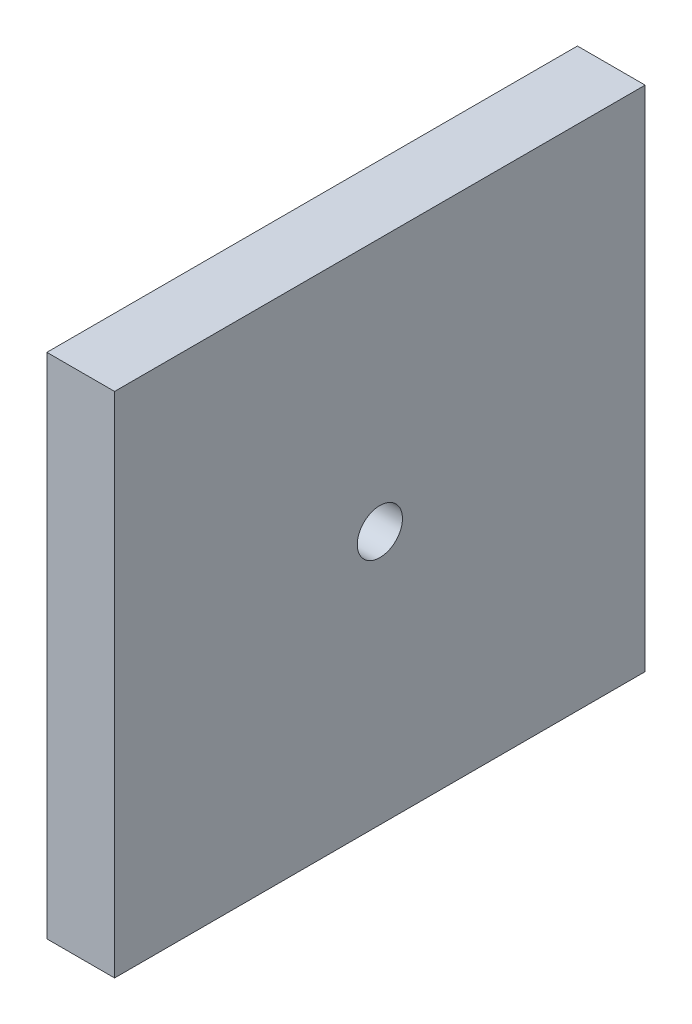
SolidWorks part; units mm, degrees
ref_plane "Ebene vorne" through (0, 0, 0) normal (0, 0, 1) x (1, 0, 0)
ref_plane "Ebene oben" through (0, 0, 0) normal (0, 1, 0) x (1, 0, 0)
ref_plane "Ebene rechts" through (0, 0, 0) normal (1, 0, 0) x (0, 0, -1)
sketch "Sketch1" plane through (0, 0, 0) normal (1, 0, 0) x (0, 0, -1)
  line L0 (0, 39.4227) -> (0, -41.65) construction
  line L1 (-47, 45) -> (47, 45)
  line L2 (-47, 45) -> (-47, -45)
  line L3 (-47, -45) -> (47, -45)
  line L4 (47, 45) -> (47, -45)
  line L5 (48.1091, 0) -> (-28.5091, 0) construction
  dimension "D1" = 94
  dimension "D2" = 90
extrude "Boss-Extrude1" add sketch "Sketch1" along normal blind 12
sketch "Sketch2" plane through (12, 0, 0) normal (1, 0, 0) x (0, 0, -1)
  circle A0 centre (0, 0) radius 4
  dimension "D1" = 8
extrude "Cut-Extrude1" cut sketch "Sketch2" against normal through all
